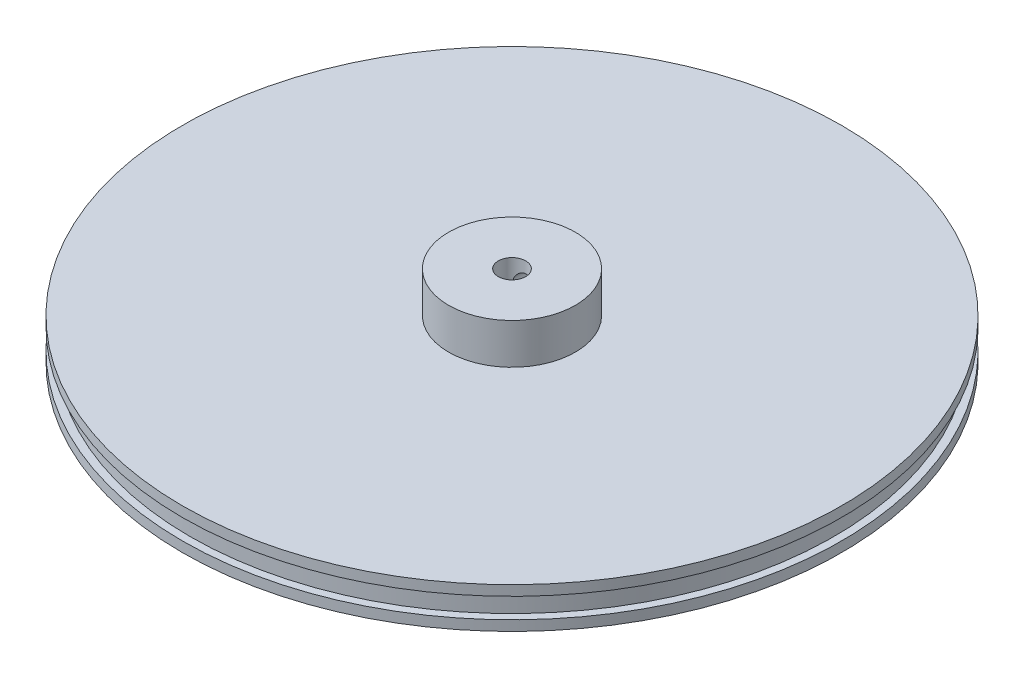
SolidWorks part; units mm, degrees
ref_plane "Front Plane" through (0, 0, 0) normal (0, 0, 1) x (1, 0, 0)
ref_plane "Top Plane" through (0, 0, 0) normal (0, 1, 0) x (1, 0, 0)
ref_plane "Right Plane" through (0, 0, 0) normal (1, 0, 0) x (0, 0, -1)
sketch "Sketch1" plane through (0, 0, 0) normal (0, 1, 0) x (1, 0, 0)
  circle A0 centre (0, 0) radius 32.5
  circle A1 centre (0, 0) radius 6.25
  circle A2 centre (0, 0) radius 1.35
  dimension "D1" = 2.7
  dimension "D2" = 65
  dimension "D3" = 12.5
extrude "Boss-Extrude1" add sketch "Sketch1" along normal blind 4 contours A2 | A0 region at (0, 0, 0)
extrude "Boss-Extrude2" add sketch "Sketch1<3>" along normal blind 8 contours A1 A2 region at (-6.0732, 0, 0)
sketch "Sketch1<3>" plane through (0, 0, 0) normal (0, 1, 0) x (1, 0, 0) same geometry as "Sketch1"
sketch "Sketch2" plane through (0, 0, 0) normal (0, 0, 1) x (1, 0, 0)
  line L0 (32.5, 0) -> (32.5, 4) construction
  line L1 (32.5, 3) -> (31.75, 3)
  line L2 (32.5, 3) -> (32.5, 1)
  line L3 (32.5, 1) -> (31.75, 1)
  line L4 (31.75, 3) -> (31.75, 1)
  line L5 (32.5, 4) -> (-32.5, 4) construction
  line L6 (-32.5, 0) -> (32.5, 0) construction
  dimension "D1" = 1
  dimension "D2" = 1
  dimension "D3" = 0.75
revolve "Cut-Revolve1" cut sketch "Sketch2" angle 360 about axis through (0, 4, 0) along (0, -1, 0)
sketch "Sketch3" plane through (0, 0, 0) normal (0, 0, 1) x (1, 0, 0)
  line L0 (0, 8) -> (0, 0) construction
  line L1 (6.25, 8) -> (-6.25, 8) construction
  circle A0 centre (0, 6) radius 0.9
  dimension "D1" = 1.8
  dimension "D2" = 2
extrude "Cut-Extrude1" cut sketch "Sketch3" against normal blind 10
